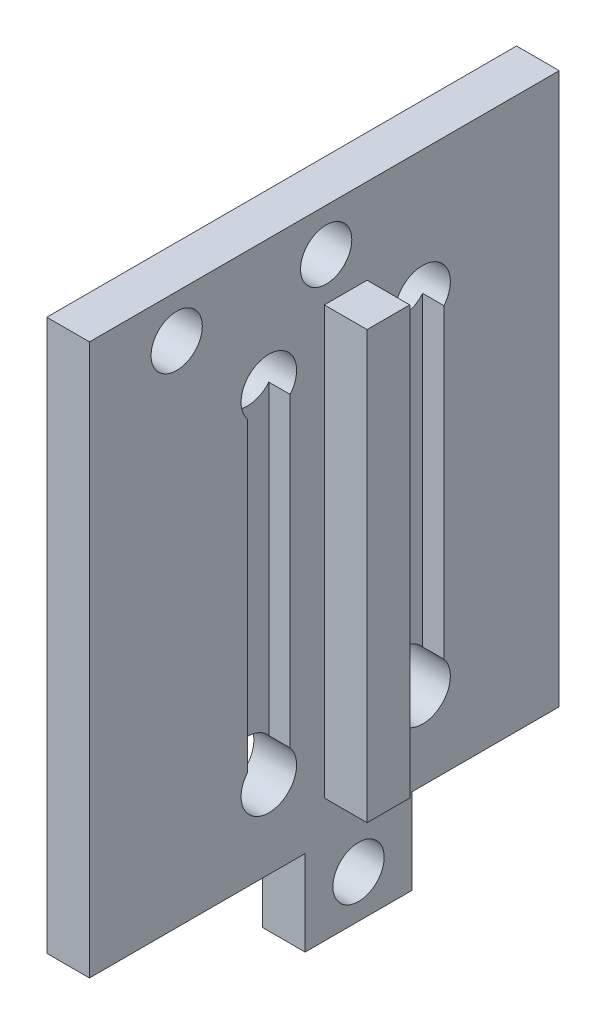
SolidWorks part; units mm, degrees
note: The reader was unsure of these and kept them because the rebuilt part matched: shared geometry of "草图1<4>".
ref_plane "前视基准面" through (0, 0, 0) normal (0, 0, 1) x (1, 0, 0)
ref_plane "上视基准面" through (0, 0, 0) normal (0, 1, 0) x (1, 0, 0)
ref_plane "右视基准面" through (0, 0, 0) normal (1, 0, 0) x (0, 0, -1)
other "Configuration Table"
sketch "草图1" plane through (0, 0, 0) normal (1, 0, 0) x (0, 0, -1)
  line L9 (0, 0) -> (10, 0)
  line L10 (0, 0) -> (0, -10)
  line L11 (0, -10) -> (10, -10)
  line L12 (10, 0) -> (10, -10)
  line L13 (0, 0) -> (10, 0)
  line L14 (0, 0) -> (0, 2)
  line L15 (0, 2) -> (10, 2)
  line L16 (10, 0) -> (10, 2)
  line L17 (4.5, 0) -> (5.5, 0)
  line L18 (4.5, 0) -> (4.5, -10)
  line L19 (4.5, -10) -> (5.5, -10)
  line L20 (5.5, 0) -> (5.5, -10)
  line L21 (0, 2) -> (-1, 2)
  line L22 (0, 2) -> (0, -10.9)
  line L23 (0, -10.9) -> (-1, -10.9)
  line L24 (-1, 2) -> (-1, -10.9)
  line L25 (0, -10.9) -> (10, -10.9)
  line L26 (0, -10.9) -> (0, -10)
  line L27 (0, -10) -> (10, -10)
  line L28 (10, -10.9) -> (10, -10)
  line L29 (4.05, -12.9) -> (6.55, -12.9)
  line L30 (4.05, -12.9) -> (4.05, -10.9)
  line L31 (4.05, -10.9) -> (6.55, -10.9)
  line L32 (6.55, -12.9) -> (6.55, -10.9)
  circle A5 centre (5.3, -11.9) radius 0.6
  circle A6 centre (1.0423, 1) radius 0.6
  circle A9 centre (4.5423, 1) radius 0.6
  circle A10 centre (3.2, -1) radius 0.65
  circle A11 centre (6.8, -1) radius 0.65
  circle A12 centre (3.2, -9) radius 0.65
  circle A14 centre (6.8, -9) radius 0.65
  point P10 (0, 0)
  point P11 (5, 0)
  point P23 (4.05, -11.9)
  point P24 (5.3, -12.9)
  point P33 (0, 0)
  dimension "D1" = 10
  dimension "D4" = 1
  dimension "D10" = 1.2
  dimension "D13" = 1.3
  dimension "D2" = 10
  dimension "D3" = 2
  dimension "D5" = 1
  dimension "D6" = 0.9
  dimension "D7" = 2
  dimension "D8" = 3.45
  dimension "D9" = 2.5
  dimension "D11" = 1.3
  dimension "D12" = 1.3
  dimension "D14" = 1
  dimension "D15" = 1
extrude "凸台-拉伸1" add sketch "草图1" along normal blind 1 contours L9 L16 L15 L14 | L12 L9 L10 L11 | L18 L9 L10 L11 | L9 L20 L11 L12 | L25 L28 L11 L22 | L29 L32 L25 L30 | L21 L24 L23 L22 L10 L14
extrude "凸台-拉伸2" add sketch "草图1<4>" along normal blind 1 from surface at 1 contours L20 L13 L18 L11 starting at face at (1, -8.175, -4.9)
sketch "草图1<4>" plane through (0, 0, 0) normal (1, 0, 0) x (0, 0, -1) same geometry as "草图1"
sketch "草图2" plane through (1, 0, 0) normal (1, 0, 0) x (0, 0, -1)
  line L1 (7.3, -1.4153) -> (6.3, -1.4153)
  line L2 (7.3, -1.4153) -> (7.3, -9.4153)
  line L3 (7.3, -9.4153) -> (6.3, -9.4153)
  line L4 (6.3, -1.4153) -> (6.3, -9.4153)
  line L5 (3.7, -1.4153) -> (2.7, -1.4153)
  line L6 (3.7, -1.4153) -> (3.7, -9.4153)
  line L7 (3.7, -9.4153) -> (2.7, -9.4153)
  line L8 (2.7, -1.4153) -> (2.7, -9.4153)
  circle A0 centre (6.8, -1) radius 0.65 construction
  circle A1 centre (3.2, -1) radius 0.65 construction
  dimension "D1" = 1
  dimension "D2" = 8
extrude "切除-拉伸1" cut sketch "草图2" against normal blind 0.5 contours L2 L3 L4 L1 | L6 L7 L8 L5
